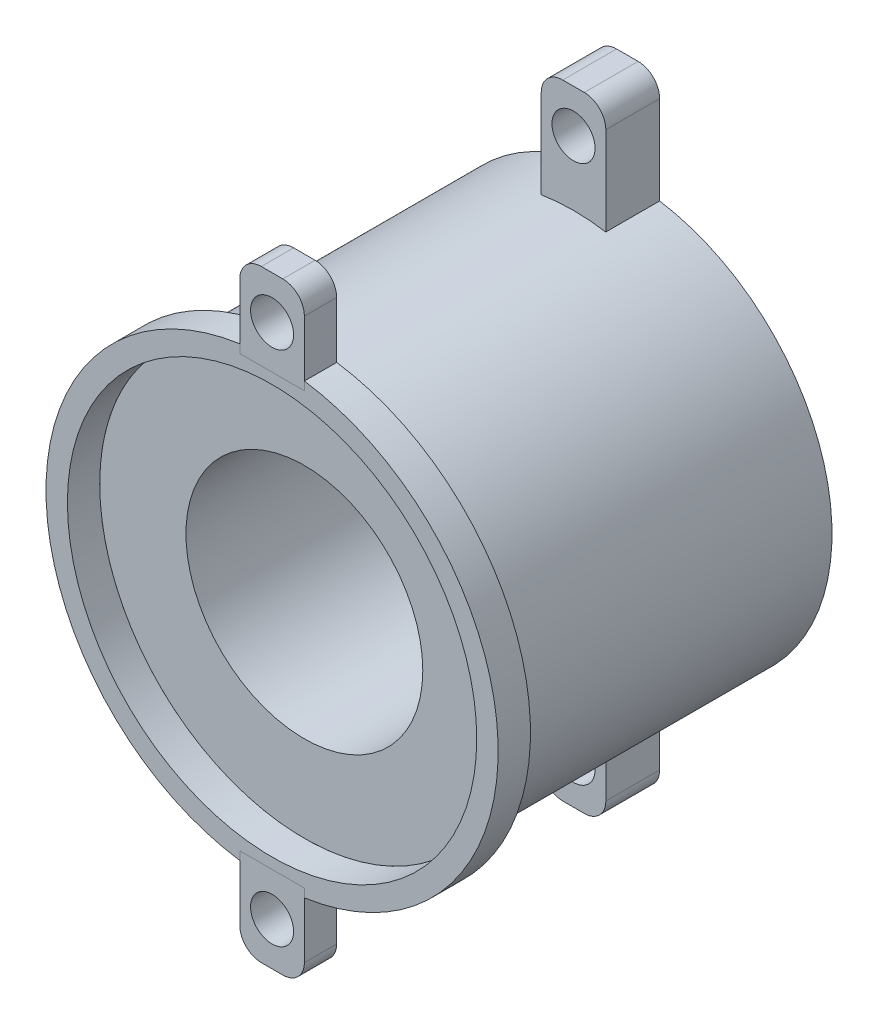
SolidWorks part; units mm, degrees
ref_plane "Front Plane" through (0, 0, 0) normal (0, 0, 1) x (1, 0, 0)
ref_plane "Top Plane" through (0, 0, 0) normal (0, 1, 0) x (1, 0, 0)
ref_plane "Right Plane" through (0, 0, 0) normal (1, 0, 0) x (0, 0, -1)
sketch "Sketch1" plane through (0, 0, 0) normal (0, 0, 1) x (1, 0, 0)
  circle A0 centre (0, 0) radius 11
  circle A1 centre (0, 0) radius 19.01
extrude "Boss-Extrude1" add sketch "Sketch1" along normal blind 30
sketch "Sketch2" plane through (0, 0, 30) normal (0, 0, 1) x (1, 0, 0)
  circle A0 centre (0, 0) radius 21
  circle A1 centre (0, 0) radius 19.01
extrude "Boss-Extrude2" add sketch "Sketch2" along normal blind 3
sketch "Sketch3" plane through (0, 0, 0) normal (0, 0, -1) x (-1, 0, 0)
  line L0 (10.6859, 5.46) -> (15.2884, 7.4137)
  line L1 (13.3348, 12.0162) -> (8.7322, 10.0625)
  line L2 (13.3348, 12.0162) -> (17.2421, 2.8111)
  line L3 (17.2421, 2.8111) -> (12.6396, 0.8575)
  line L4 (8.7322, 10.0625) -> (12.6396, 0.8575)
  point P2 (10.6859, 5.46)
  point P6 (15.2884, 7.4137)
  dimension "D1" = 12
  dimension "D2" = 5.46
extrude "Cut-Extrude1" cut sketch "Sketch3" against normal offset from surface (28 mm away) 2 contours L1 L4 L3 L2 up to face at (19.01, 0, 30)
mirror "Mirror1" about plane through (0, 0, 0) normal (0, 1, 0) of "Cut-Extrude1"
mirror "Mirror2" about plane through (0, 0, 0) normal (1, 0, 0) of "Mirror1"
sketch "Sketch4" plane through (0, 0, 0) normal (0, 0, -1) x (-1, 0, 0)
  line L1 (-3, 29) -> (3, 29)
  line L2 (-3, 29) -> (-3, 17)
  line L3 (-3, 17) -> (3, 17)
  line L4 (3, 29) -> (3, 17)
  circle A0 centre (0, 25) radius 2
  point P4 (0, 17)
  dimension "D1" = 8
  dimension "D2" = 17
extrude "Boss-Extrude3" add sketch "Sketch4" along normal blind 0.0001 and the other way blind 5
fillet "Fillet1" radius 2 2 edges at (3, 29, 2.5) (-3, 29, 2.5)
mirror "Mirror5" about plane through (0, 0, 0) normal (0, 1, 0) of "Fillet1", "Boss-Extrude3"
sketch "Sketch7" plane through (0, 0, 33) normal (0, 0, 1) x (1, 0, 0)
  line L1 (-3, 28) -> (3, 28)
  line L2 (-3, 28) -> (-3, 20)
  line L3 (-3, 20) -> (3, 20)
  line L4 (3, 28) -> (3, 20)
  circle A0 centre (0, 24) radius 2
  point P4 (0, 20)
  point P8 (0, 0)
  point P9 (0, 0)
  dimension "D1" = 20
  dimension "D2" = 4
extrude "Boss-Extrude6" add sketch "Sketch7" along normal blind 0.0001 and the other way blind 3
mirror "Mirror6" about plane through (0, 0, 0) normal (0, 1, 0) of "Boss-Extrude6"
fillet "Fillet2" radius 2 4 edges at (-3, 28, 31.5001) (3, 28, 31.5001) (3, -28, 31.5001) (-3, -28, 31.5001)
